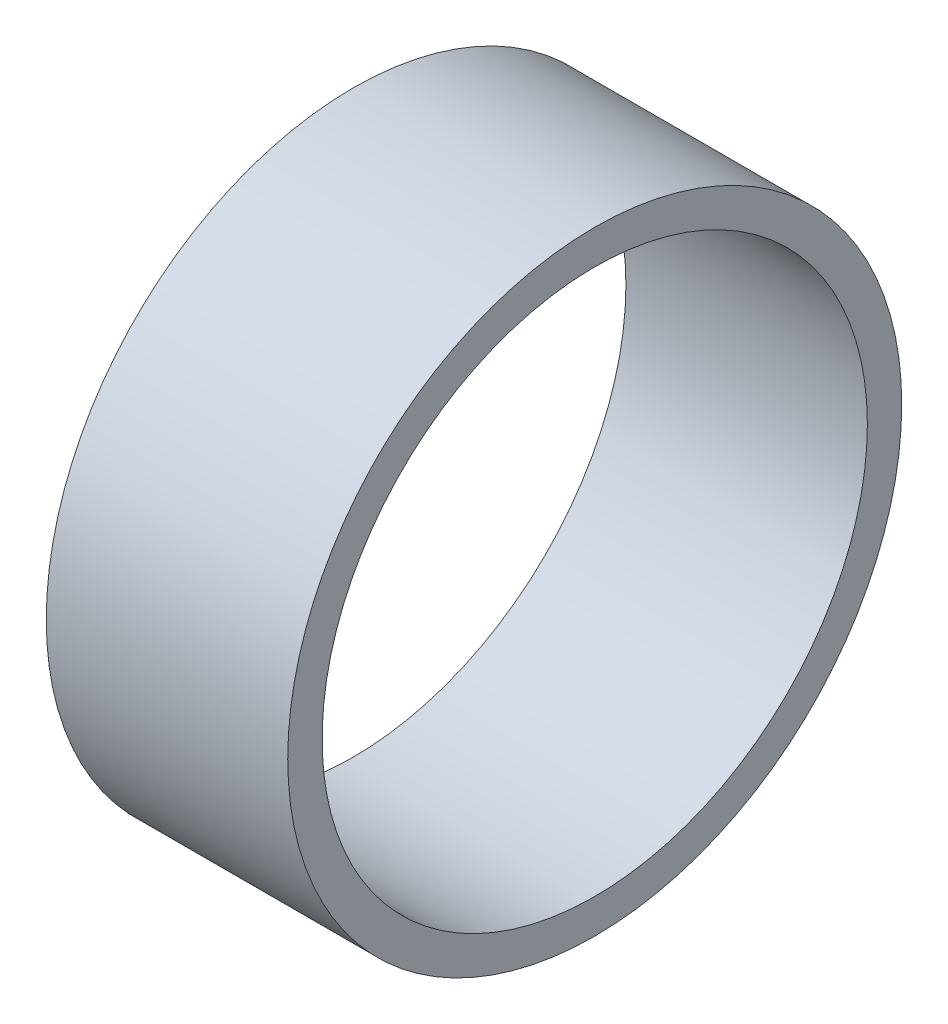
SolidWorks part; units mm, degrees
material "Nylon 6/10"
ref_plane "Front Plane" through (0, 0, 0) normal (0, 0, 1) x (1, 0, 0)
ref_plane "Top Plane" through (0, 0, 0) normal (0, 1, 0) x (1, 0, 0)
ref_plane "Right Plane" through (0, 0, 0) normal (1, 0, 0) x (0, 0, -1)
sketch "Sketch1" plane through (0, 0, 0) normal (0, 0, 1) x (1, 0, 0)
  line L0 (-25.4, 7.5) -> (-42.95, 7.5) construction
  line L1 (-39.521, 8.7312) -> (-32.654, 8.7312)
  line L2 (-39.521, 8.7312) -> (-39.521, 7.754)
  line L3 (-39.521, 7.754) -> (-32.654, 7.754)
  line L4 (-32.654, 8.7312) -> (-32.654, 7.754)
  line L5 (-39.775, 7.2673) -> (-39.775, 12.1553) construction
  line L6 (-32.4, 15.2446) -> (-32.4, -15.2446) construction
  line L7 (0, 0) -> (-47.1489, 0) construction
  dimension "D1" = 0.254
  dimension "D2" = 0.254
  dimension "D3" = 0.254
  dimension "D4" = 17.4625
revolve "Revolve1" add sketch "Sketch1" angle 360 about L7
